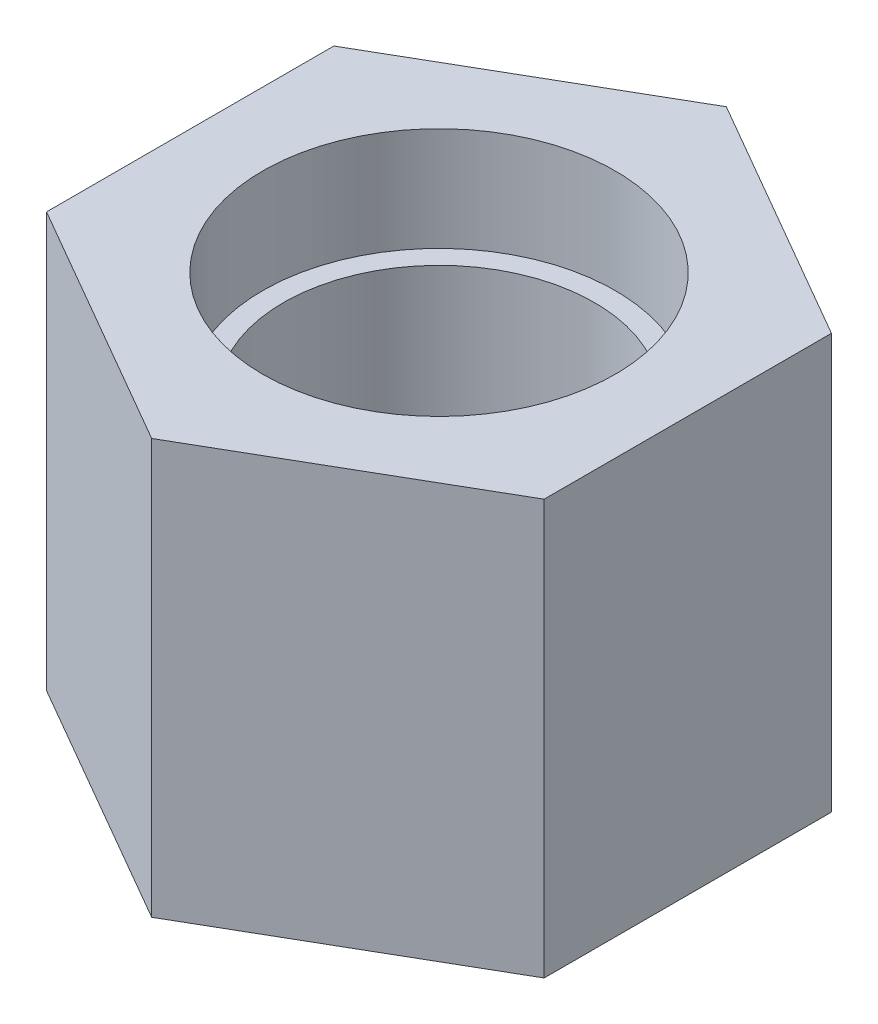
SolidWorks part; units mm, degrees
ref_plane "Спереди" through (0, 0, 0) normal (0, 0, 1) x (1, 0, 0)
ref_plane "Сверху" through (0, 0, 0) normal (0, 1, 0) x (1, 0, 0)
ref_plane "Справа" through (0, 0, 0) normal (1, 0, 0) x (0, 0, -1)
sketch "Эскиз1" plane through (0, 0, 0) normal (0, 1, 0) x (1, 0, 0)
  line L1 (0, 13.8564) -> (-12, 6.9282)
  line L2 (-12, 6.9282) -> (-12, -6.9282)
  line L3 (-12, -6.9282) -> (0, -13.8564)
  line L4 (0, -13.8564) -> (12, -6.9282)
  line L5 (12, -6.9282) -> (12, 6.9282)
  line L6 (12, 6.9282) -> (0, 13.8564)
  circle A0 centre (0, 0) radius 12 construction
  circle A1 centre (0, 0) radius 7.5
extrude "Бобышка-Вытянуть1" add sketch "Эскиз1" along normal blind 20
sketch "Эскиз3" plane through (0, 20, 0) normal (0, 1, 0) x (1, 0, 0)
  circle A0 centre (0, 0) radius 8.5
extrude "Вырез-Вытянуть2" cut sketch "Эскиз3" against normal blind 5
